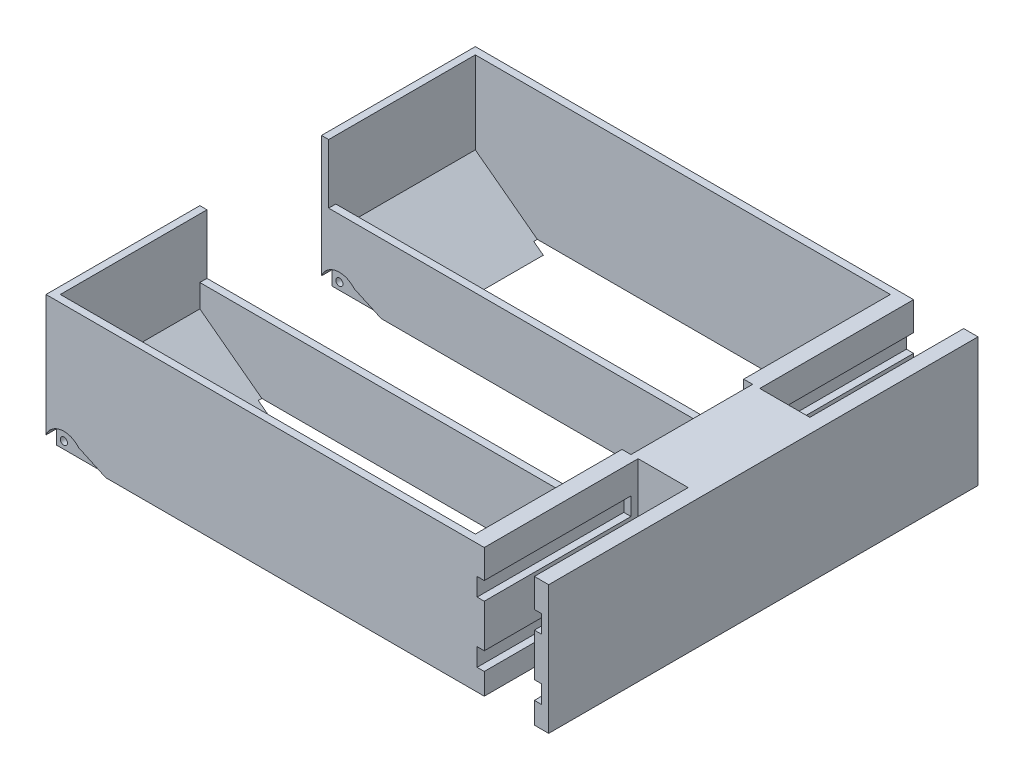
SolidWorks part; units mm, degrees
ref_plane "Front Plane" through (0, 0, 0) normal (0, 0, 1) x (1, 0, 0)
ref_plane "Top Plane" through (0, 0, 0) normal (0, 1, 0) x (1, 0, 0)
ref_plane "Right Plane" through (0, 0, 0) normal (1, 0, 0) x (0, 0, -1)
sketch "Sketch2" plane through (0, 0, 0) normal (0, 1, 0) x (1, 0, 0)
  line L1 (-60, -21.5) -> (60, -21.5)
  line L2 (-60, -21.5) -> (-60, 21.5)
  line L3 (-60, 21.5) -> (60, 21.5)
  line L4 (60, -21.5) -> (60, 21.5)
  line L5 (-60, -21.5) -> (60, 21.5) construction
  line L6 (-60, 21.5) -> (60, -21.5) construction
  point P0 (0, 0)
  dimension "D1" = 120
  dimension "D2" = 43
extrude "Boss-Extrude1" add sketch "Sketch2" along normal blind 38 contours L2 L3 L4 L1
sketch "Sketch3" plane through (0, 38, 0) normal (0, 1, 0) x (1, 0, 0)
  line L0 (-60, 21.5) -> (60, 21.5) construction
  line L1 (-58, -19.5) -> (58, -19.5)
  line L2 (-58, -19.5) -> (-58, 19.5)
  line L3 (-58, 19.5) -> (58, 19.5)
  line L4 (58, -19.5) -> (58, 19.5)
  line L5 (-58, -19.5) -> (58, 19.5) construction
  line L6 (-58, 19.5) -> (58, -19.5) construction
  line L7 (60, -21.5) -> (60, 21.5) construction
  point P0 (0, 0)
  dimension "D1" = 2
  dimension "D2" = 2
extrude "Cut-Extrude1" cut sketch "Sketch3" against normal up to vertex (38 mm away) up to point (-60, 0, -21.5)
sketch "Sketch4" plane through (0, 0, -19.5) normal (0, 0, 1) x (1, 0, 0)
  line L0 (-58, 0) -> (-58, 15)
  line L1 (-58, 15) -> (-38, 0)
  line L2 (-60, 0) -> (60, 0) construction
  line L3 (-38, 0) -> (-58, 0)
  dimension "D1" = 15
  dimension "D2" = 20
extrude "Boss-Extrude2" add sketch "Sketch4" along normal up to vertex (39 mm away) up to point (-58, 0, 19.5)
sketch "Sketch5" plane through (60, 0, 0) normal (1, 0, 0) x (0, 0, -1)
  line L1 (-21.5, 38) -> (21.5, 38)
  line L2 (-21.5, 38) -> (-21.5, 0)
  line L3 (-21.5, 0) -> (21.5, 0)
  line L4 (21.5, 38) -> (21.5, 0)
extrude "Boss-Extrude3" add sketch "Sketch5" along normal blind 2.5
sketch "Sketch6" plane through (0, 0, -21.5) normal (0, 0, -1) x (-1, 0, 0)
  line L0 (60, 0) -> (-62.5, 0) construction
  line L1 (-62.5, 38) -> (-60.5, 38)
  line L2 (-62.5, 38) -> (-62.5, 0)
  line L3 (-62.5, 0) -> (-60.5, 0)
  line L4 (-60.5, 38) -> (-60.5, 0)
  dimension "D1" = 2
extrude "Boss-Extrude4" add sketch "Sketch6" along normal blind 17 contours L4 L3 L2 L1
ref_plane "Plane1" through (0, 0, -38.5) normal (0, 0, -1) x (-1, 0, 0)
mirror "Mirror1" about plane through (0, 0, -38.5) normal (0, 0, -1) of bodies 105
sketch "Sketch7" plane through (62.5, 0, 0) normal (1, 0, 0) x (0, 0, -1)
  line L0 (38.5, 38) -> (38.5, 0) construction
  line L1 (98.5, 38) -> (-21.5, 38) construction
  line L2 (-21.5, 0) -> (98.5, 0) construction
  line L3 (-21.5, 19) -> (98.5, 19) construction
  line L4 (-21.5, 38) -> (-21.5, 0) construction
  line L5 (98.5, 38) -> (98.5, 0) construction
  line L11 (21.5, 0) -> (55.5, 0)
  line L12 (21.5, 0) -> (21.5, 38)
  line L13 (21.5, 38) -> (55.5, 38)
  line L14 (55.5, 0) -> (55.5, 38)
  line L15 (21.5, 0) -> (55.5, 38) construction
  line L16 (21.5, 38) -> (55.5, 0) construction
  point P12 (38.5, 19)
  point P13 (38.5, 19)
  dimension "D1" = 34
extrude "Boss-Extrude5" add sketch "Sketch7" along normal blind 18
sketch "Sketch8" plane through (0, 0, -21.5) normal (0, 0, 1) x (1, 0, 0)
  line L0 (80.5, 0) -> (62.5, 0) construction
  line L1 (80.5, 38) -> (76.5, 38)
  line L2 (80.5, 38) -> (80.5, 0)
  line L3 (80.5, 0) -> (76.5, 0)
  line L4 (76.5, 38) -> (76.5, 0)
  dimension "D1" = 4
extrude "Boss-Extrude6" add sketch "Sketch8" along normal up to vertex (43 mm away) up to point (62.5, 38, 21.5)
sketch "Sketch9" plane through (0, 0, 21.5) normal (0, 0, 1) x (1, 0, 0)
  line L0 (78.5, 38) -> (78.5, 0) construction
  line L1 (80.5, 38) -> (76.5, 38) construction
  line L2 (76.5, 0) -> (80.5, 0) construction
  line L3 (78.5, 19) -> (52.6863, 19) construction
  line L4 (78.5, 30) -> (60.5, 30)
  line L5 (78.5, 30) -> (78.5, 25)
  line L6 (78.5, 25) -> (60.5, 25)
  line L7 (60.5, 30) -> (60.5, 25)
  line L8 (78.5, 13) -> (60.5, 13)
  line L9 (60.5, 8) -> (60.5, 13)
  line L10 (78.5, 8) -> (60.5, 8)
  line L11 (78.5, 8) -> (78.5, 13)
  dimension "D1" = 18
  dimension "D2" = 5
  dimension "D3" = 25
extrude "Cut-Extrude2" cut sketch "Sketch9" against normal up to vertex (41 mm away) up to point (58, 38, -19.5)
mirror "Mirror2" about plane through (0, 0, -38.5) normal (0, 0, -1) of "Boss-Extrude6", "Cut-Extrude2"
sketch "Sketch11" plane through (80.5, 0, 0) normal (1, 0, 0) x (0, 0, -1)
  line L0 (98.5, 0) -> (98.5, 38) construction
  line L1 (-21.5, 0) -> (98.5, 0)
  line L2 (-21.5, 0) -> (-21.5, 2)
  line L3 (-21.5, 2) -> (98.5, 2)
  line L4 (98.5, 0) -> (98.5, 2)
  dimension "D1" = 2
extrude "Cut-Extrude3" cut sketch "Sketch11" against normal up to vertex (118.5 mm away) up to point (-38, 0, 19.5)
sketch "Sketch12" plane through (0, 0, 21.5) normal (0, 0, 1) x (1, 0, 0)
  line L0 (-60, 38) -> (-60, 0) construction
  line L1 (-38, 2) -> (-49.6148, 2)
  line L2 (-38, 2) -> (-38, 0)
  line L3 (-38, 0) -> (-60, 0)
  arc A0 (-49.6148, 2) -> (-60, 0) centre (-55, 2) ccw
  dimension "D1" = 5
extrude "Cut-Extrude4" cut sketch "Sketch12" against normal blind 3
ref_plane "Plane2" through (0, 0, 0) normal (0, 0, 1) x (1, 0, 0)
mirror "Mirror3" about plane through (0, 0, 0) normal (0, 0, 1) of "Cut-Extrude4"
mirror "Mirror4" about plane through (0, 0, -38.5) normal (0, 0, -1) of "Mirror3", "Cut-Extrude4"
sketch "Sketch13" plane through (0, 0, 18.5) normal (0, 0, 1) x (1, 0, 0)
  line L0 (-60, 0) -> (-38, 0) construction
  line L1 (-60, 0) -> (-60, 4) construction
  circle A0 centre (-58, 2) radius 1
  dimension "D1" = 2
  dimension "D2" = 2
  dimension "D3" = 2
extrude "Cut-Extrude5" cut sketch "Sketch13" against normal up to vertex (117 mm away) up to point (-60, 4, -98.5)
chamfer "Chamfer1" distance 10 angle 45 1 edges at (-49.6148, 2, 20)
chamfer "Chamfer2" distance 10 angle 45 1 edges at (-49.6148, 2, -20)
chamfer "Chamfer3" distance 10 angle 45 1 edges at (-49.6148, 2, -57)
chamfer "Chamfer4" distance 10 angle 45 1 edges at (-49.6148, 2, -97)
sketch "Sketch14" plane through (0, 38, 0) normal (0, 1, 0) x (1, 0, 0)
  line L0 (-60, 21.5) -> (60.5, 21.5) construction
  line L1 (-58, 19.5) -> (58, 19.5)
  line L2 (-58, 19.5) -> (-58, 21.5)
  line L3 (-58, 21.5) -> (58, 21.5)
  line L4 (58, 19.5) -> (58, 21.5)
  dimension "D1" = 116
extrude "Cut-Extrude6" cut sketch "Sketch14" against normal blind 16.6
mirror "Mirror5" about plane through (0, 0, -38.5) normal (0, 0, -1) of "Cut-Extrude6"
sketch "Sketch15" plane through (0, 0, -21.5) normal (0, 0, 1) x (1, 0, 0)
  line L0 (62.5, 25) -> (62.5, 13) construction
  line L1 (62.5, 2) -> (76.5, 2) construction
  circle A0 centre (70.2, 21.1) radius 1.75
  dimension "D1" = 3.5
  dimension "D2" = 7.7
  dimension "D3" = 19.1
extrude "Cut-Extrude7" cut sketch "Sketch15" against normal blind 1
mirror "Mirror6" about plane through (0, 0, -38.5) normal (0, 0, -1) of "Cut-Extrude7"
